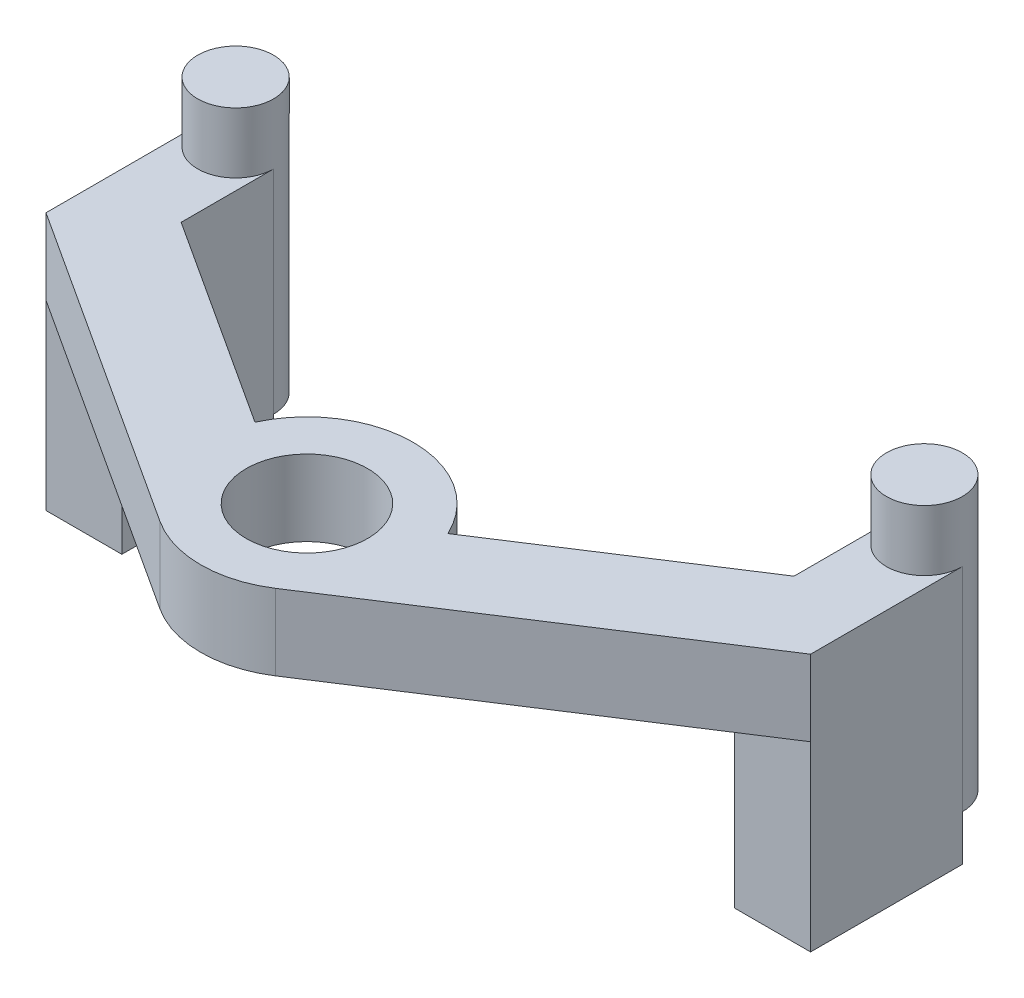
SolidWorks part; units mm, degrees
ref_plane "Plano frontal" through (0, 0, 0) normal (0, 0, 1) x (1, 0, 0)
ref_plane "Plano superior" through (0, 0, 0) normal (0, 1, 0) x (1, 0, 0)
ref_plane "Plano direito" through (0, 0, 0) normal (1, 0, 0) x (0, 0, -1)
sketch "Esboço1" plane through (0, 0, 0) normal (0, 1, 0) x (1, 0, 0)
  line L0 (0, 0) -> (0, 9.6236) construction
  line L1 (-10.1, 9) -> (-10.1, 5.9543)
  line L2 (-10.1, 5.9543) -> (-3.1785, 1.4654)
  line L3 (10.1, 9) -> (10.1, 5.9543)
  line L4 (-12.6, 9) -> (-12.6, 4)
  line L5 (-12.6, 4) -> (-1.9044, -2.9365)
  line L6 (10.1, 5.9543) -> (3.1785, 1.4654)
  line L7 (12.6, 4) -> (1.9044, -2.9365)
  line L8 (12.6, 9) -> (12.6, 4)
  line L9 (-12.6, 4) -> (-10.1, 4)
  line L10 (-10.1, 4) -> (-10.1, 5.9543)
  line L11 (10.1, 4) -> (10.1, 5.9543)
  line L12 (12.6, 4) -> (10.1, 4)
  circle A0 centre (0, 0) radius 2
  circle A1 centre (0, 0) radius 3.5
  circle A2 centre (-11.35, 9) radius 1.25
  circle A3 centre (11.35, 9) radius 1.25
  dimension "D1" = 4
  dimension "D2" = 7
  dimension "D3" = 2.5
  dimension "D4" = 22.7
  dimension "D5" = 9
  dimension "D6" = 5
  dimension "D7" = 3
extrude "Ressalto-extrusão1" add sketch "Esboço1" against normal blind 2.5 contours A2 | A2 L4 L9 L10 L1 | A1 L2 L10 L9 L5 | A0 A1 | A1 L7 L12 L11 L6 | A3 L3 L11 L12 L8 | A3 region at (-11.35, 0, -9) region at (-11.35, 0, -6.0188) region at (-7.0165, 0, -2.051) region at (0, 0, -3.401) region at (7.0165, 0, -2.051) region at (11.35, 0, -6.0188) region at (11.35, 0, -9)
extrude "Ressalto-extrusão2" add sketch "Esboço1<3>" against normal blind 7 contours A2 L4 L9 L10 L1 | A2 | A3 | A3 L3 L11 L12 L8 region at (-11.35, 0, -9) region at (-11.35, 0, -6.0188) region at (11.35, 0, -6.0188) region at (11.35, 0, -9)
sketch "Esboço1<3>" plane through (0, 0, 0) normal (0, 1, 0) x (1, 0, 0) same geometry as "Esboço1"
extrude "Ressalto-extrusão3" add sketch "Esboço1<4>" along normal blind 2 contours A2 | A3 region at (-11.35, 0, -9) region at (11.35, 0, -9)
sketch "Esboço1<4>" plane through (0, 0, 0) normal (0, 1, 0) x (1, 0, 0) same geometry as "Esboço1"
sketch "Esboço2" plane through (0, -7, 0) normal (0, -1, 0) x (1, 0, 0)
  line L0 (-10.1, -9) -> (-12.6, -9)
  line L1 (-12.6, -9) -> (-12.6, -4)
  line L2 (-12.6, -4) -> (-10.1, -4)
  line L3 (-10.1, -4) -> (-10.1, -9)
  line L4 (10.1, -9) -> (12.6, -9)
  line L5 (12.6, -9) -> (12.6, -4)
  line L6 (12.6, -4) -> (10.1, -4)
  line L7 (10.1, -4) -> (10.1, -9)
  arc A0 (10.1, -9) -> (12.6, -9) centre (11.35, -9) ccw construction
extrude "Ressalto-extrusão4" add sketch "Esboço2" along normal blind 1.5
